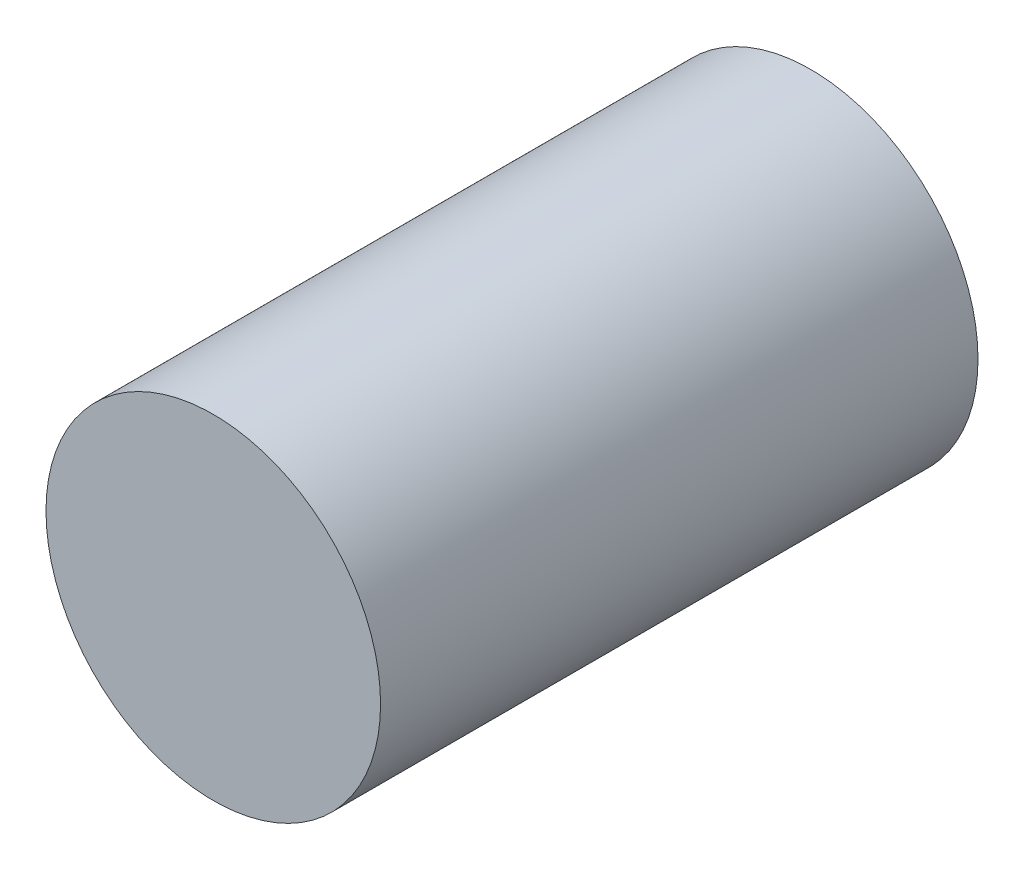
SolidWorks part; units mm, degrees
ref_plane "Front Plane" through (0, 0, 0) normal (0, 0, 1) x (1, 0, 0)
ref_plane "Top Plane" through (0, 0, 0) normal (0, 1, 0) x (1, 0, 0)
ref_plane "Right Plane" through (0, 0, 0) normal (1, 0, 0) x (0, 0, -1)
sketch "Esquisse1" plane through (0, 0, 0) normal (0, 0, 1) x (1, 0, 0)
  circle A0 centre (0, 0) radius 7
extrude "Boss.-Extru.1" add sketch "Esquisse1" along normal blind 35
sketch "Esquisse2" plane through (0, 0, 35) normal (0, 0, 1) x (1, 0, 0)
  circle A0 centre (0, 0) radius 9.8018
extrude "Enlèv. mat.-Extru.3" cut sketch "Esquisse2" against normal blind 5
ref_axis "Axe1" through (0, 0, 30) along (0, 0, -1)
sketch "Esquisse3" plane through (0, 0, 30) normal (0, 0, 1) x (1, 0, 0)
  line L1 (-10.8881, 7.1106) -> (8.0488, 7.1106)
  line L2 (-10.8881, 7.1106) -> (-10.8881, -7.5797)
  line L3 (-10.8881, -7.5797) -> (8.0488, -7.5797)
  line L4 (8.0488, 7.1106) -> (8.0488, -7.5797)
extrude "Enlèv. mat.-Extru.4" cut sketch "Esquisse3" against normal blind 5
